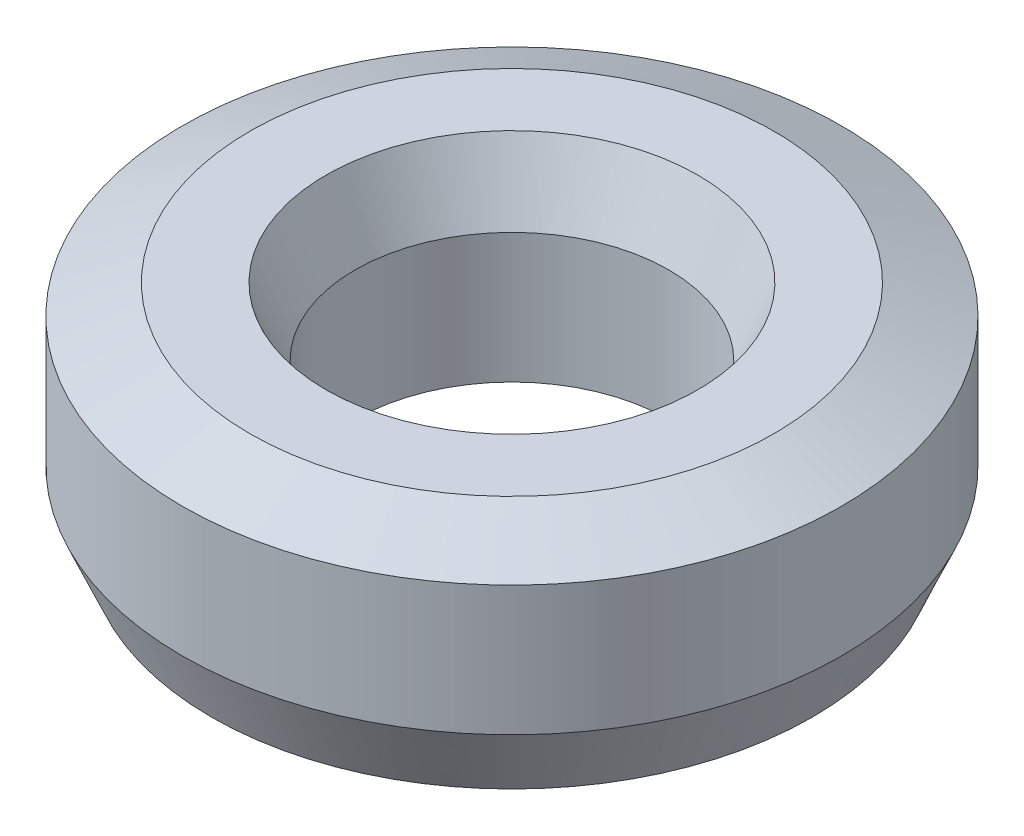
SolidWorks part; units mm, degrees
ref_plane "Front Plane" through (0, 0, 0) normal (0, 0, 1) x (1, 0, 0)
ref_plane "Top Plane" through (0, 0, 0) normal (0, 1, 0) x (1, 0, 0)
ref_plane "Right Plane" through (0, 0, 0) normal (1, 0, 0) x (0, 0, -1)
sketch "Sketch1" plane through (0, 0, 0) normal (0, 1, 0) x (1, 0, 0)
  circle A0 centre (0, 0) radius 7.5
  dimension "SLEEVE_OD" = 15
extrude "Boss-Extrude1" add sketch "Sketch1" along normal blind 5.1489
sketch "Sketch2" plane through (0, 0, 0) normal (0, 1, 0) x (1, 0, 0)
  circle A0 centre (0, 0) radius 3.5701
  dimension "BORE_D" = 7.1401
extrude "Cut-Extrude1" cut sketch "Sketch2" along normal through all
chamfer "Chamfer1" distance 0.662 angle 66.696 4 edges at (0, 5.1489, 3.5701) (0, 0, 3.5701) (0, 0, 7.5) (0, 5.1489, 7.5) first distance on face at (0, 5.1489, 3.5701) first distance on face at (0, 0, 3.5701) first distance on face at (0, 5.1489, 7.5)
